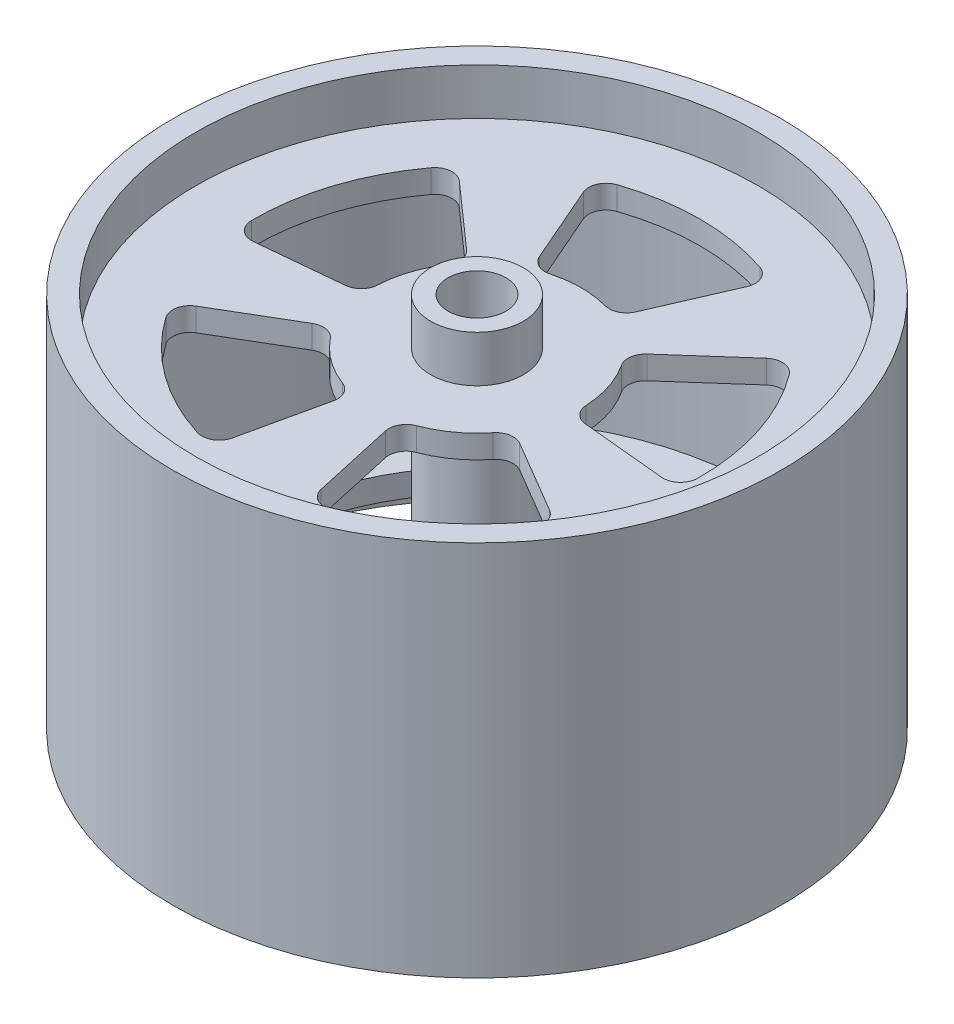
SolidWorks part; units mm, degrees
ref_plane "Front Plane" through (0, 0, 0) normal (0, 0, 1) x (1, 0, 0)
ref_plane "Top Plane" through (0, 0, 0) normal (0, 1, 0) x (1, 0, 0)
ref_plane "Right Plane" through (0, 0, 0) normal (1, 0, 0) x (0, 0, -1)
sketch "Sketch1" plane through (0, 0, 0) normal (0, 1, 0) x (1, 0, 0)
  circle A0 centre (0, 0) radius 52.5
  circle A1 centre (0, 0) radius 48.5
  dimension "D1" = 105
  dimension "D2" = 97
extrude "Boss-Extrude1" add sketch "Sketch1" along normal blind 65
sketch "Sketch2" plane through (0, 0, 0) normal (0, -1, 0) x (1, 0, 0)
  line L0 (7.6561, 34.5345) -> (4.4986, 20.2919)
  line L1 (7.6085, 2.4721) -> (46.1262, 14.9873)
  line L2 (0, 8) -> (0, 48.5)
  line L3 (30.4784, 17.9532) -> (17.9086, 10.549)
  line L4 (35.2102, 3.3904) -> (20.6889, 1.9921)
  line L5 (26.4928, -23.4389) -> (15.5668, -13.7723)
  line L6 (14.105, -32.4392) -> (8.2878, -19.0607)
  line L7 (-14.105, -32.4392) -> (-8.2878, -19.0607)
  line L8 (-26.4928, -23.4389) -> (-15.5668, -13.7723)
  line L9 (-35.2102, 3.3904) -> (-20.6889, 1.9921)
  line L10 (-30.4784, 17.9532) -> (-17.9086, 10.549)
  line L11 (-7.6561, 34.5345) -> (-4.4986, 20.2919)
  arc A0 (46.1262, 14.9873) -> (0, 48.5) centre (0, 0) ccw
  circle A1 centre (0, 0) radius 5
  circle A2 centre (0, 0) radius 8
  arc A3 (14.0452, 11.2576) -> (6.3664, 16.8365) centre (0, 0) ccw
  arc A4 (31.4028, 22.2737) -> (11.4795, 36.7488) centre (0, 0) ccw
  arc A5 (6.3664, 16.8365) -> (4.4986, 20.2919) centre (7.4275, 19.6426) cw
  arc A6 (17.9086, 10.549) -> (14.0452, 11.2576) centre (16.386, 13.1339) cw
  arc A7 (31.4028, 22.2737) -> (30.4784, 17.9532) centre (28.9558, 20.538) cw
  arc A8 (11.4795, 36.7488) -> (7.6561, 34.5345) centre (10.585, 33.8852) ccw
  arc A9 (38.4975, 0.4383) -> (35.2102, 3.3904) centre (35.4977, 0.4042) ccw
  arc A10 (30.8875, -22.9829) -> (38.4975, 0.4383) centre (0, 0) ccw
  arc A11 (30.8875, -22.9829) -> (26.4928, -23.4389) centre (28.4807, -21.192) cw
  arc A12 (15.5668, -13.7723) -> (15.0468, -9.8789) centre (17.5546, -11.5254) cw
  arc A13 (15.0468, -9.8789) -> (17.9798, -0.8521) centre (0, 0) ccw
  arc A14 (17.9798, -0.8521) -> (20.6889, 1.9921) centre (20.9765, -0.9941) cw
  arc A15 (12.3132, -36.4779) -> (14.105, -32.4392) centre (11.3538, -33.6354) ccw
  arc A16 (-12.3132, -36.4779) -> (12.3132, -36.4779) centre (0, 0) ccw
  arc A17 (-12.3132, -36.4779) -> (-14.105, -32.4392) centre (-11.3538, -33.6354) cw
  arc A18 (-8.2878, -19.0607) -> (-4.7457, -17.3631) centre (-5.5367, -20.257) cw
  arc A19 (-4.7457, -17.3631) -> (4.7457, -17.3631) centre (0, 0) ccw
  arc A20 (4.7457, -17.3631) -> (8.2878, -19.0607) centre (5.5367, -20.257) cw
  arc A21 (-30.8875, -22.9829) -> (-26.4928, -23.4389) centre (-28.4807, -21.192) ccw
  arc A22 (-38.4975, 0.4383) -> (-30.8875, -22.9829) centre (0, 0) ccw
  arc A23 (-38.4975, 0.4383) -> (-35.2102, 3.3904) centre (-35.4977, 0.4042) cw
  arc A24 (-20.6889, 1.9921) -> (-17.9798, -0.8521) centre (-20.9765, -0.9941) cw
  arc A25 (-17.9798, -0.8521) -> (-15.0468, -9.8789) centre (0, 0) ccw
  arc A26 (-15.0468, -9.8789) -> (-15.5668, -13.7723) centre (-17.5546, -11.5254) cw
  arc A27 (-31.4028, 22.2737) -> (-30.4784, 17.9532) centre (-28.9558, 20.538) ccw
  arc A28 (-11.4795, 36.7488) -> (-31.4028, 22.2737) centre (0, 0) ccw
  arc A29 (-11.4795, 36.7488) -> (-7.6561, 34.5345) centre (-10.585, 33.8852) cw
  arc A30 (-4.4986, 20.2919) -> (-6.3664, 16.8365) centre (-7.4275, 19.6426) cw
  arc A31 (-6.3664, 16.8365) -> (-14.0452, 11.2576) centre (0, 0) ccw
  arc A32 (-14.0452, 11.2576) -> (-17.9086, 10.549) centre (-16.386, 13.1339) cw
  point P71 (0, 0)
  circle M12 centre (0, 0) radius 48.5
  dimension "D1" = 97
  dimension "D2" = 10
  dimension "D3" = 3
  dimension "D6" = 10
  dimension "D7" = 10
  dimension "D10" = 3
  dimension "D4" = 72
  dimension "D5" = 72
  dimension "D8" = 12.5
  dimension "D9" = 12.5
  dimension "D11" = 5
extrude "Boss-Extrude2" add sketch "Sketch2" against normal blind 65 separate body contours A2 A1 region at (7.678, 0, 1.2161)
extrude "Boss-Extrude3" add sketch "Sketch2<3>" against normal blind 4 from offset 8 contours A2 L1 L2 A8 A4 A7 L3 A6 A3 A5 L0 M12 | A2 L2 L1 A13 A14 L4 A9 A10 A11 L5 A12 A19 A20 L6 A15 A16 A17 L7 A18 A25 A26 L8 A21 A22 A23 L9 A24 A31 A32 L10 A27 A28 A29 L11 A30 M12 region at (5.0853, 0, 6.9993) region at (-4.7092, 0, -6.4817) offset against normal yes
sketch "Sketch2<3>" plane through (0, 0, 0) normal (0, -1, 0) x (1, 0, 0) same geometry as "Sketch2"
extrude "Boss-Extrude4" add sketch "Sketch2<4>" against normal blind 4 from offset 53 contours A2 L2 L1 A13 A14 L4 A9 A10 A11 L5 A12 A19 A20 L6 A15 A16 A17 L7 A18 A25 A26 L8 A21 A22 A23 L9 A24 A31 A32 L10 A27 A28 A29 L11 A30 M12 | A2 L1 L2 A8 A4 A7 L3 A6 A3 A5 L0 M12 region at (5.0853, 0, 6.9993) region at (-4.7092, 0, -6.4817) offset against normal yes
sketch "Sketch2<4>" plane through (0, 0, 0) normal (0, -1, 0) x (1, 0, 0) same geometry as "Sketch2"
